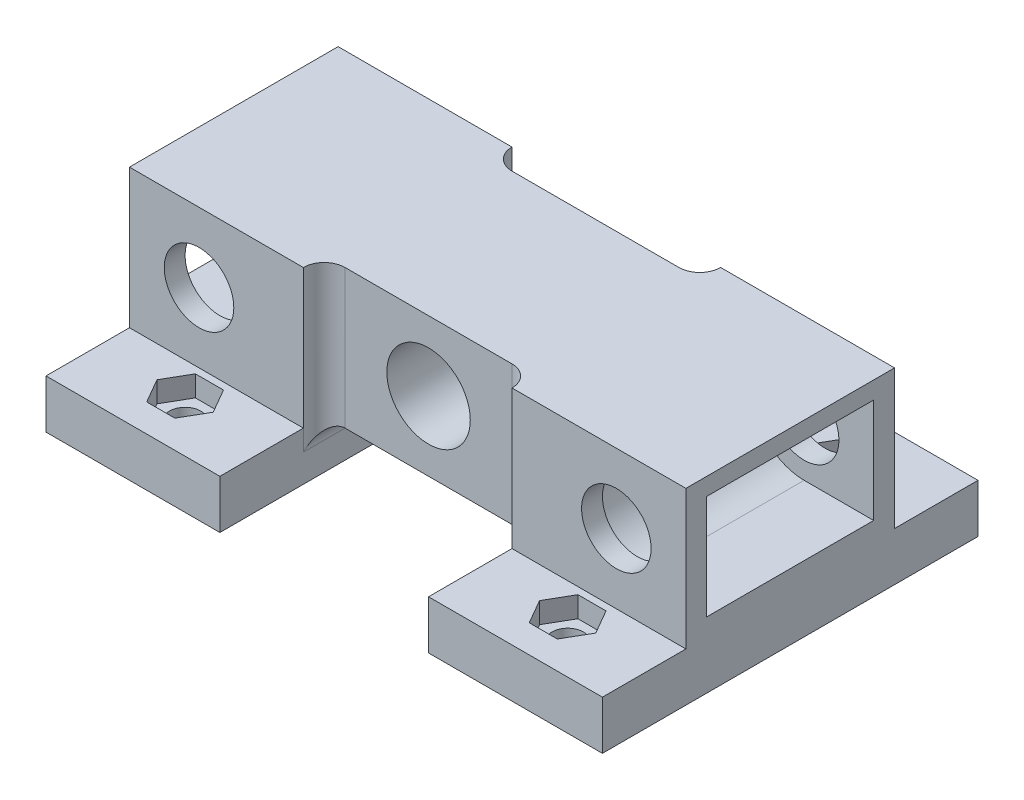
SolidWorks part; units mm, degrees
ref_plane "Plan de face" through (0, 0, 0) normal (0, 0, 1) x (1, 0, 0)
ref_plane "Plan de dessus" through (0, 0, 0) normal (0, 1, 0) x (1, 0, 0)
ref_plane "Plan de droite" through (0, 0, 0) normal (1, 0, 0) x (0, 0, -1)
sketch "Sketch1" plane through (0, 0, 0) normal (0, 0, 1) x (1, 0, 0)
  line L1 (40, -10) -> (-40, -10)
  line L2 (40, -10) -> (40, 10)
  line L3 (40, 10) -> (-40, 10)
  line L4 (-40, -10) -> (-40, 10)
  line L5 (40, -10) -> (-40, 10) construction
  line L6 (40, 10) -> (-40, -10) construction
  circle A0 centre (0, 0) radius 6
  circle A1 centre (30, 0) radius 7.5
  circle A2 centre (-30, 0) radius 7.5
  dimension "D1" = 12
  dimension "D2" = 15
  dimension "D4" = 15
  dimension "D3" = 30
  dimension "D5" = 30
  dimension "D6" = 20
  dimension "D7" = 80
extrude "Boss-Extrude1" add sketch "Sketch1" along normal blind 12 and the other way blind 12
sketch "Sketch2" plane through (0, -10, 0) normal (0, -1, 0) x (1, 0, 0)
  line L0 (40, -12) -> (40, 12) construction
  line L1 (40, -27) -> (15, -27)
  line L2 (40, -27) -> (40, 27)
  line L3 (40, 27) -> (15, 27)
  line L4 (15, -27) -> (15, 27)
  line L5 (-40, 12) -> (40, 12) construction
  line L6 (-40, -12) -> (40, -12) construction
  line L7 (0, -55) -> (0, 55) construction
  line L8 (-40, 27) -> (-15, 27)
  line L9 (-15, -27) -> (-15, 27)
  line L10 (-40, -27) -> (-15, -27)
  line L11 (-40, -27) -> (-40, 27)
  dimension "D1" = 25
  dimension "D2" = 15
  dimension "D3" = 15
extrude "Boss-Extrude2" add sketch "Sketch2" along normal blind 7
sketch "Sketch3" plane through (0, -10, 0) normal (0, 1, 0) x (1, 0, 0)
  line L0 (15, 12) -> (15, 27) construction
  line L1 (29.5207, 23) -> (25.4793, 23)
  line L2 (25.4793, 23) -> (23.4585, 19.5)
  line L3 (23.4585, 19.5) -> (25.4793, 16)
  line L4 (25.4793, 16) -> (29.5207, 16)
  line L5 (29.5207, 16) -> (31.5415, 19.5)
  line L6 (31.5415, 19.5) -> (29.5207, 23)
  circle A0 centre (27.5, 19.5) radius 3.5 construction
  dimension "D1" = 12.5
extrude "Cut-Extrude1" cut sketch "Sketch3" against normal blind 3
mirror "Mirror1" about plane through (0, 0, 0) normal (1, 0, 0) of "Cut-Extrude1"
mirror "Mirror2" about plane through (0, 0, 0) normal (0, 0, 1) of "Mirror1"
hole_wizard "Dégagement M41" positions "Sketch4" profile "Sketch5" hole size "M4" standard "ISO" end condition through all
sketch "Sketch4" plane through (0, -13, 0) normal (0, 1, 0) x (1, 0, 0)
  line L1 (-40, 27) -> (-15, 27) construction
  line L2 (-40, 12) -> (-40, 27) construction
  line L3 (15, 12) -> (15, 27) construction
  line L4 (15, 27) -> (40, 27) construction
  line L5 (-15, -27) -> (-40, -27) construction
  line L6 (-15, -12) -> (-15, -27) construction
  line L7 (40, -27) -> (15, -27) construction
  line L8 (40, -12) -> (40, -27) construction
  point P0 (27.5, 19.5)
  point P2 (27.5, -19.5)
  point P4 (-27.5, -19.5)
  point P6 (-27.5, 19.5)
  dimension "D1" = 7.5
  dimension "D2" = 12.5
  dimension "D3" = 12.5
  dimension "D4" = 7.5
  dimension "D5" = 7.5
  dimension "D6" = 12.5
  dimension "D7" = 7.5
  dimension "D8" = 12.5
sketch "Sketch5" plane through (27.5, -13, -19.5) normal (1, 0, 0) x (0, 0, 1)
  line L0 (0, 0) -> (0, 4)
  line L1 (0, 4) -> (2.25, 4)
  line L2 (2.25, 4) -> (2.25, 0)
  line L5 (2.25, 0) -> (0, 0)
  line L11 (0, -6.35) -> (0, 107.95) construction
  dimension "Diamètre du perçage jusqu'au prochain" = 4.5
  dimension "Profondeur du perçage jusqu'au prochain" = 4
sketch "Sketch6" plane through (0, 0, -12) normal (0, 0, -1) x (-1, 0, 0)
  line L0 (-30, 7.5) -> (-40, 7.5)
  line L1 (-30, -7.5) -> (-40, -7.5)
  line L2 (-40, -10) -> (-40, 10) construction
  line L3 (-40, -7.5) -> (-40, 7.5)
  circle A0 centre (-30, 0) radius 7.5 construction
  arc A1 (-30, 7.5) -> (-30, -7.5) centre (-30, 0) ccw
extrude "Cut-Extrude2" cut sketch "Sketch6" against normal through all
mirror "Mirror3" about plane through (0, 0, 0) normal (1, 0, 0) of "Cut-Extrude2"
sketch "Sketch7" plane through (0, 0, -12) normal (0, 0, -1) x (-1, 0, 0)
  line L1 (-40, 10) -> (-15, 10)
  line L2 (-40, 10) -> (-40, -10)
  line L3 (-40, -10) -> (-15, -10)
  line L4 (-15, 10) -> (-15, -10)
  line L5 (40, 10) -> (15, 10)
  line L6 (40, 10) -> (40, -10)
  line L7 (40, -10) -> (15, -10)
  line L8 (15, 10) -> (15, -10)
extrude "Boss-Extrude3" add sketch "Sketch7" along normal blind 3
sketch "Sketch8" plane through (0, 0, 12) normal (0, 0, 1) x (1, 0, 0)
  line L0 (40, 10) -> (-40, 10) construction
  line L1 (40, -10) -> (15, -10)
  line L2 (40, -10) -> (40, 10)
  line L3 (40, 10) -> (15, 10)
  line L4 (15, -10) -> (15, 10)
  line L5 (15, -17) -> (15, -10) construction
  line L7 (-40, 10) -> (-15, 10)
  line L8 (-40, 10) -> (-40, -10)
  line L9 (-40, -10) -> (-15, -10)
  line L10 (-15, 10) -> (-15, -10)
extrude "Boss-Extrude4" add sketch "Sketch8" along normal blind 3
sketch "Sketch10" plane through (0, 0, -12) normal (0, 0, 1) x (1, 0, 0)
  line L0 (0, -14.85) -> (0, 14.85) construction
  circle A0 centre (30, 0) radius 5
  circle A1 centre (-30, 0) radius 5
  dimension "D1" = 10
extrude "Cut-Extrude3" cut sketch "Sketch10" against normal through all both and the other way through all
fillet "Fillet1" radius 3 6 edges at (15, -10, 0) (-15, -10, 0) (-15, 0, -12) (15, 0, -12) (-15, 0, 12) (15, 0, 12)
